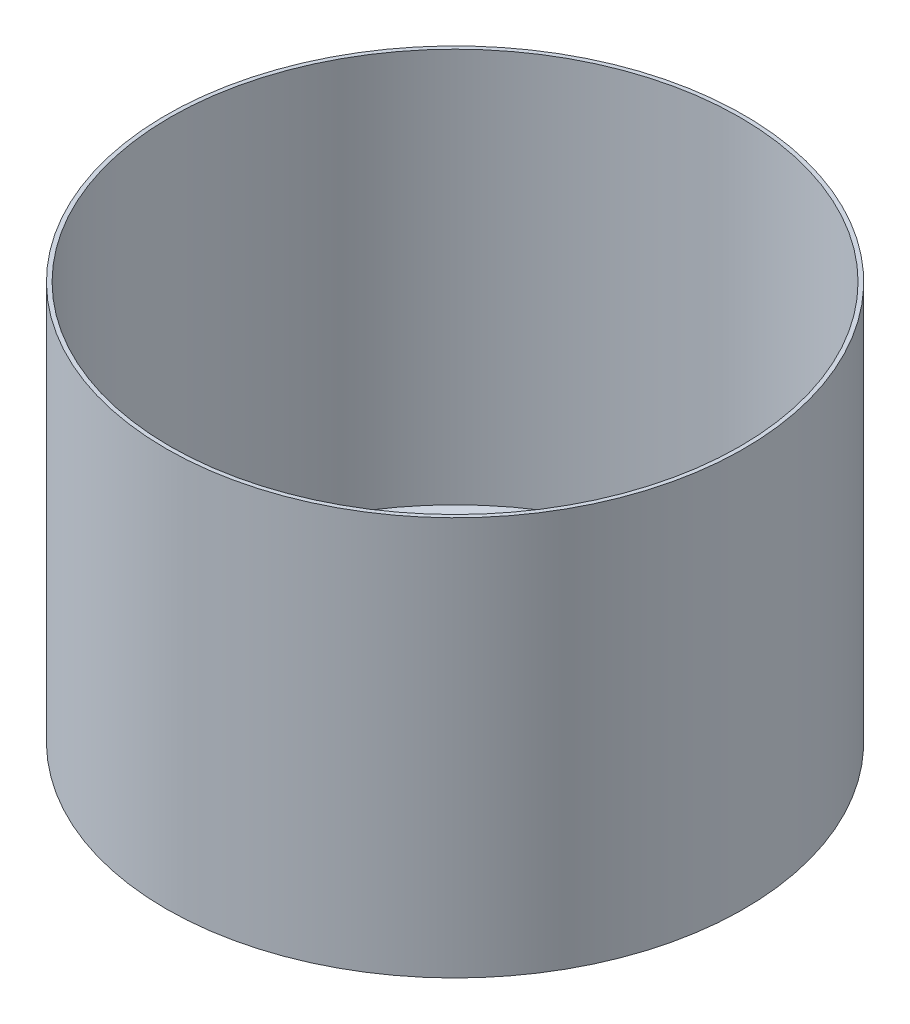
SolidWorks part; units mm, degrees
ref_plane "前基準面" through (0, 0, 0) normal (0, 0, 1) x (1, 0, 0)
ref_plane "上基準面" through (0, 0, 0) normal (0, 1, 0) x (1, 0, 0)
ref_plane "右基準面" through (0, 0, 0) normal (1, 0, 0) x (0, 0, -1)
sketch "草圖6" plane through (0, 0, 0) normal (0, 1, 0) x (1, 0, 0)
  line L0 (0, 0) -> (0, 28.8688) construction
  circle A0 centre (0, 0) radius 72.5
  circle A1 centre (-5, 0) radius 2
  circle A3 centre (5, 0) radius 2
  circle A4 centre (0, 5) radius 2
  circle A5 centre (5, 0) radius 2
  circle A6 centre (0, -5) radius 2
  circle A7 centre (0, 0) radius 71.5
  point P17 (0, 0)
  dimension "D1" = 145
  dimension "D3" = 4
  dimension "D4" = 1
  dimension "D2" = 10
extrude "填料-伸長2" add sketch "草圖6" along normal blind 1 contours A7 A3 A1 A4 A6 region at (0, 0, 0)
extrude "填料-伸長3" add sketch "草圖6<7>" along normal blind 100 contours A0 A7 region at (-72.2949, 0, 0)
sketch "草圖6<7>" plane through (0, 0, 0) normal (0, 1, 0) x (1, 0, 0) same geometry as "草圖6"
